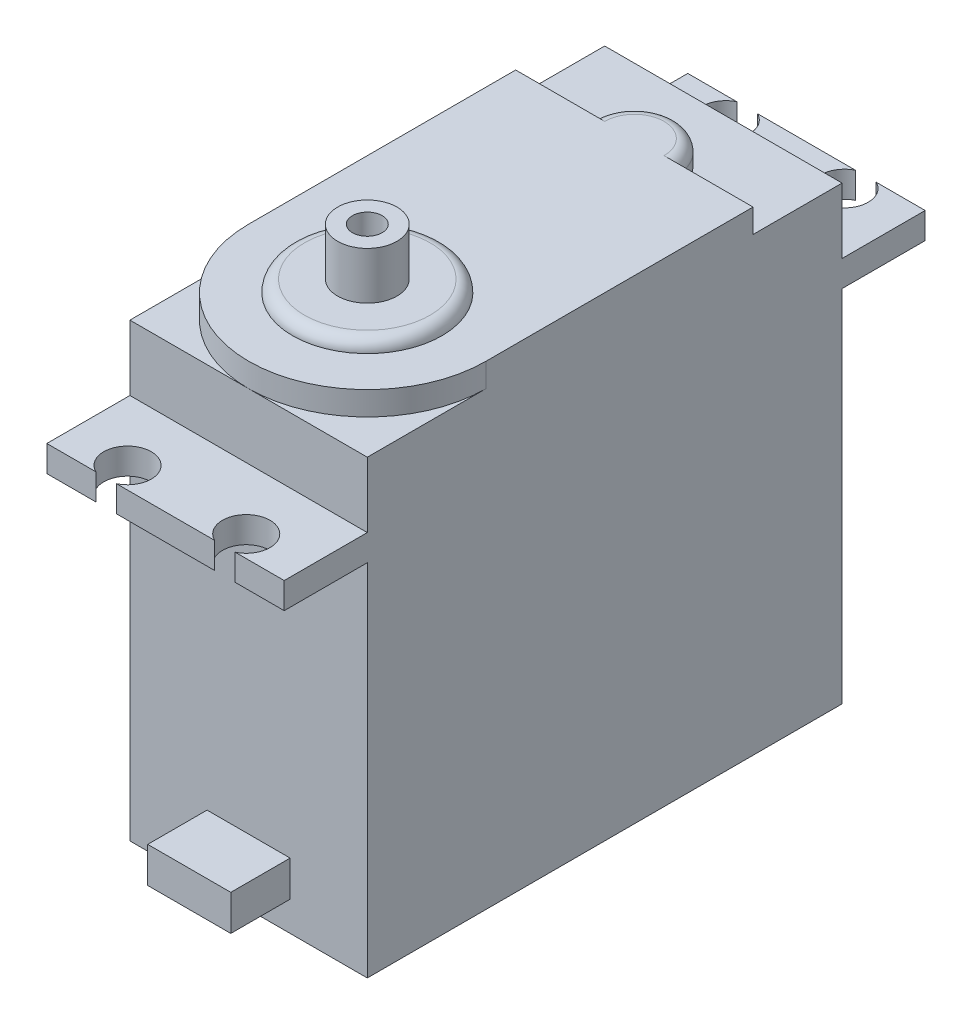
SolidWorks part; units mm, degrees
material "PVC 0.007 Plasticized"
ref_plane "Front Plane" through (0, 0, 0) normal (0, 0, 1) x (1, 0, 0)
ref_plane "Top Plane" through (0, 0, 0) normal (0, 1, 0) x (1, 0, 0)
ref_plane "Right Plane" through (0, 0, 0) normal (1, 0, 0) x (0, 0, -1)
sketch "Sketch1" plane through (0, 0, 0) normal (0, 1, 0) x (1, 0, 0)
  line L1 (0, 0) -> (20, 0)
  line L2 (0, 0) -> (0, 40)
  line L3 (0, 40) -> (20, 40)
  line L4 (20, 0) -> (20, 40)
  dimension "D1" = 40
  dimension "D2" = 20
extrude "Boss-Extrude1" add sketch "Sketch1" along normal blind 38
sketch "Sketch2" plane through (0, 0, 0) normal (0, 0, 1) x (1, 0, 0)
  line L0 (6.5, 2.5) -> (0, 0) construction
  line L1 (6.5, 2.5) -> (13.5, 2.5)
  line L2 (6.5, 2.5) -> (6.5, 5.5)
  line L3 (6.5, 5.5) -> (13.5, 5.5)
  line L4 (13.5, 2.5) -> (13.5, 5.5)
  line L5 (13.5, 2.5) -> (20, 0) construction
  line L6 (0, 0) -> (20, 0) construction
  dimension "D1" = 7
  dimension "D2" = 3
  dimension "." = 2.5
extrude "Boss-Extrude2" add sketch "Sketch2" along normal blind 5
sketch "Sketch3" plane through (0, 38, 0) normal (0, 1, 0) x (1, 0, 0)
  line L0 (0, 0) -> (20, 0) construction
  line L1 (10, 10) -> (0, 0) construction
  line L2 (10, 10) -> (20, 0) construction
  line L3 (20, 0) -> (20, 40) construction
  circle A0 centre (10, 10) radius 2.5
  dimension "D1" = 10
  dimension "D2" = 5
extrude "Boss-Extrude3" add sketch "Sketch3" along normal blind 7
sketch "Sketch4" plane through (0, 0, 0) normal (0, 0, 1) x (1, 0, 0)
  line L0 (0, 38) -> (0, 0) construction
  line L1 (0, 32.5) -> (20, 32.5)
  line L2 (0, 32.5) -> (0, 30.3)
  line L3 (0, 30.3) -> (20, 30.3)
  line L4 (20, 32.5) -> (20, 30.3)
  line L5 (20, 38) -> (20, 0) construction
  line L6 (0, 38) -> (20, 38) construction
  dimension "D1" = 2.2
  dimension "D2" = 5.5
extrude "Boss-Extrude4" add sketch "Sketch4" along normal blind 7 and the other way blind 47
sketch "Sketch5" plane through (0, 32.5, 0) normal (0, 1, 0) x (1, 0, 0)
  line L0 (15, 45.2) -> (20, 47) construction
  line L1 (5, 45.2) -> (0, 47) construction
  line L2 (5, 45.2) -> (15, 45.2) construction
  line L3 (20, 40) -> (0, 40) construction
  line L4 (15, 45.2) -> (15, -5.2) construction
  line L5 (0, 0) -> (20, 0) construction
  circle A0 centre (15, 45.2) radius 2
  circle A1 centre (5, 45.2) radius 2
  circle A2 centre (15, -5.2) radius 2
  circle A3 centre (5, -5.2) radius 2
  dimension "D1" = 4
  dimension "D2" = 10
  dimension "D3" = 5.2
  dimension "D4" = 5.2
extrude "Cut-Extrude1" cut sketch "Sketch5" against normal blind 7
sketch "Sketch6" plane through (0, 38, 0) normal (0, 1, 0) x (1, 0, 0)
  line L0 (20, 0) -> (20, 40) construction
  line L1 (20, 32.5) -> (13.5, 32.5)
  line L2 (20, 32.5) -> (20, 10)
  line L4 (0, 32.5) -> (0, 10)
  line L5 (6.5, 32.5) -> (0, 32.5)
  line L6 (0, 40) -> (0, 0) construction
  line L7 (20, 40) -> (0, 40) construction
  arc A0 (0, 10) -> (20, 10) centre (10, 10) ccw
  circle A1 centre (10, 10) radius 2.5 construction
  arc A2 (13.5, 32.5) -> (6.5, 32.5) centre (10, 32.5) ccw
  dimension "D1" = 3.5
  dimension "D2" = 7.5
extrude "Boss-Extrude5" add sketch "Sketch6" along normal blind 2
sketch "Sketch7" plane through (0, 40, 0) normal (0, 1, 0) x (1, 0, 0)
  circle A0 centre (10, 10) radius 6.2895
  circle A1 centre (10, 10) radius 2.5 construction
extrude "Boss-Extrude6" add sketch "Sketch7" along normal blind 1
fillet "Fillet1" radius 1 1 edges at (10, 41, -3.7105)
fillet "Fillet2" radius 1 1 edges at (10, 40, -36)
sketch "Sketch8" plane through (0, 45, 0) normal (0, 1, 0) x (1, 0, 0)
  circle A0 centre (10, 10) radius 1.25
  dimension "D1" = 2.5
extrude "Cut-Extrude2" cut sketch "Sketch8" against normal blind 5
